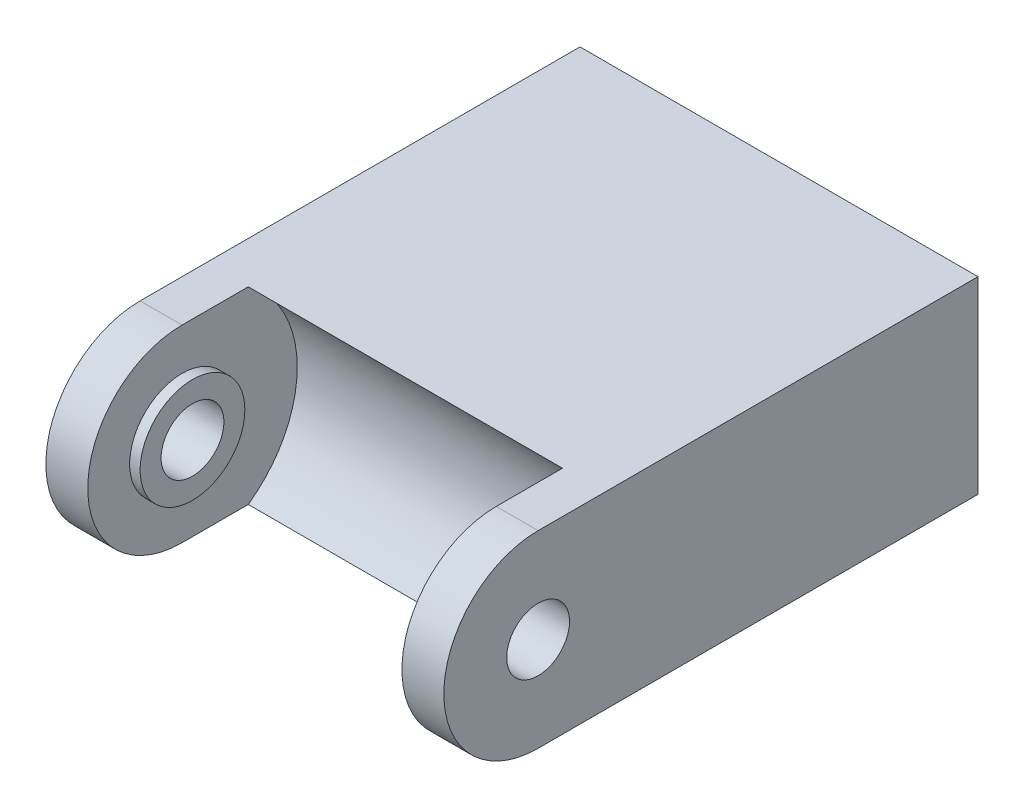
SolidWorks part; units mm, degrees
ref_plane "Front" through (0, 0, 0) normal (0, 0, 1) x (1, 0, 0)
ref_plane "Top" through (0, 0, 0) normal (0, 1, 0) x (1, 0, 0)
ref_plane "Right" through (0, 0, 0) normal (1, 0, 0) x (0, 0, -1)
sketch "Эскиз1" plane through (0, 0, 0) normal (1, 0, 0) x (0, 0, -1)
  line L0 (0, 4.5) -> (21, 4.5)
  line L1 (21, 4.5) -> (21, -4.5)
  line L2 (21, -4.5) -> (0, -4.5)
  circle A0 centre (0, 0) radius 4.5
  dimension "D1" = 9
  dimension "D2" = 21
extrude "Бобышка-Вытянуть1" add sketch "Эскиз1" along normal blind 9.5 and the other way blind 9.5 contours A0 | A0 L2 L1 L0 region at (0, 0, -12.2383) region at (0, 0, 0)
sketch "Эскиз2" plane through (0, 0, 0) normal (1, 0, 0) x (0, 0, -1)
  circle A0 centre (0, 0) radius 5.5
extrude "Вырез-Вытянуть1" cut sketch "Эскиз2" against normal blind 7 and the other way blind 7
sketch "Эскиз3" plane through (0, 0, 0) normal (1, 0, 0) x (0, 0, -1)
  circle A0 centre (0, 0) radius 1.5
extrude "Вырез-Вытянуть2" cut sketch "Эскиз3" against normal through all both and the other way through all
sketch "Эскиз4" plane through (0, 0, 0) normal (1, 0, 0) x (0, 0, -1)
  circle A0 centre (0, 0) radius 5.5
  circle A1 centre (0, 0) radius 2.5
  dimension "D1" = 5
  dimension "D2" = 11
extrude "Вырез-Вытянуть3" cut sketch "Эскиз4" against normal blind 7.5 and the other way blind 7.5
sketch "Эскиз5" plane through (0, 0, -21) normal (0, 0, -1) x (-1, 0, 0)
  circle A0 centre (0, 0) radius 1.75
extrude "Вырез-Вытянуть4" cut sketch "Эскиз5" against normal blind 2
